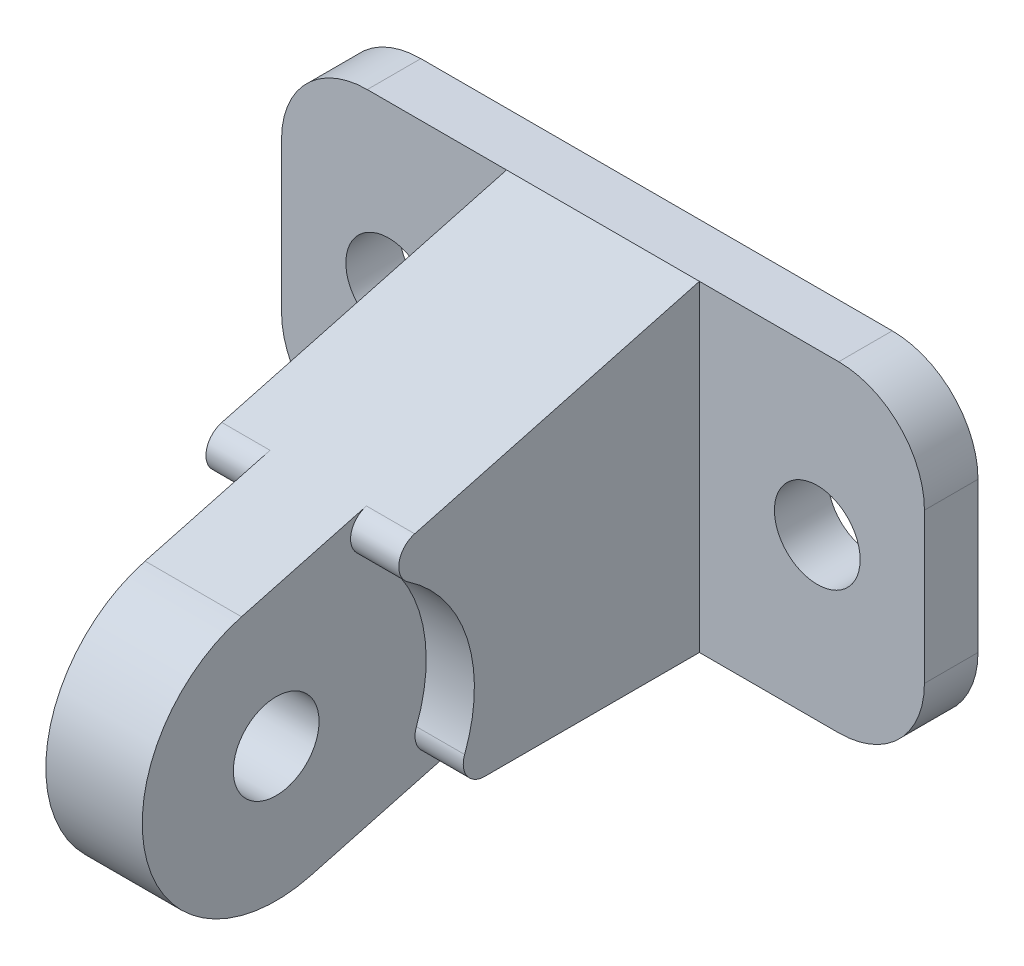
SolidWorks part; units mm, degrees
ref_plane "Front Plane" through (0, 0, 0) normal (0, 0, 1) x (1, 0, 0)
ref_plane "Top Plane" through (0, 0, 0) normal (0, 1, 0) x (1, 0, 0)
ref_plane "Right Plane" through (0, 0, 0) normal (1, 0, 0) x (0, 0, -1)
sketch "Sketch1" plane through (0, 0, 0) normal (0, 0, 1) x (1, 0, 0)
  line L1 (30, -15) -> (-30, -15)
  line L2 (30, -15) -> (30, 15)
  line L3 (30, 15) -> (-30, 15)
  line L4 (-30, -15) -> (-30, 15)
  line L5 (30, -15) -> (-30, 15) construction
  line L6 (30, 15) -> (-30, -15) construction
  point P0 (0, 0)
  dimension "D1" = 30
  dimension "D2" = 60
extrude "Boss-Extrude1" add sketch "Sketch1" along normal blind 5
sketch "Sketch3" plane through (0, 0, 0) normal (1, 0, 0) x (0, 0, -1)
  line L0 (-5, 15) -> (-31.5739, 7.8795)
  line L1 (-5, 15) -> (-5, -15)
  line L2 (-5, -15) -> (-25.0425, -15)
  line L3 (-5, 15) -> (0, 15) construction
  line L4 (-31.5739, 7.8795) -> (-43.2352, 4.7549)
  line L5 (-36.7648, -19.3932) -> (-20.3689, -15)
  arc A1 (-31.5739, 7.8795) -> (-32.1742, 4.2893) centre (-31.0563, 5.9477) ccw
  arc A2 (-25.0425, -15) -> (-26.9121, -12.2899) centre (-25.0425, -13) cw
  arc A3 (-26.9121, -12.2899) -> (-32.1742, 4.2893) centre (-40, -7.3192) ccw
  circle A4 centre (-40, -7.3192) radius 4
  circle A5 centre (-40, -7.3192) radius 12.5
  point P14 (-19.3881, -12.2899)
  point P16 (-40, -19.8192)
  point P18 (-21.4082, -15)
  point P19 (-45.0839, -21.5747)
  point P23 (-23.1859, -15)
  point P24 (-36.9289, -19.436)
  dimension "D2" = 2
  dimension "D3" = 14
  dimension "D5" = 8
  dimension "D6" = 25
  dimension "D1" = 15
  dimension "D4" = 40
extrude "Boss-Extrude2" add sketch "Sketch3" along normal mid plane 18 contours A3 A1 L0 L1 L2 A2
extrude "Boss-Extrude3" add sketch "Sketch3<3>" along normal mid plane 9 contours A5 A4 | A5 L5 L2 A2 A3 A1 L4 region at (0, 6.3362, 33.3799) region at (0, 2.3173, 32.6057)
sketch "Sketch3<3>" plane through (0, 0, 0) normal (1, 0, 0) x (0, 0, -1) same geometry as "Sketch3"
hole_wizard "Hole1" positions "Sketch4" profile "Sketch5" legacy end condition through all
sketch "Sketch4" plane through (0, 0, 5) normal (0, 0, 1) x (1, 0, 0)
  line L0 (0, 0) -> (0, 18.1868) construction
  point P0 (-20, 0)
  point P2 (20, 0)
  point P9 (0, 0)
  dimension "D1" = 40
sketch "Sketch5" plane through (-20, 0, 5) normal (1, 0, 0) x (0, -1, 0)
  line L0 (0, 0) -> (0, 5)
  line L1 (0, 5) -> (4, 5)
  line L2 (4, 5) -> (4, 0)
  line L3 (4, 0) -> (0, 0)
  line L4 (0, 110) -> (0, -10) construction
  dimension "Diameter" = 8
  dimension "Depth" = 5
fillet "Fillet1" radius 8 4 edges at (30, 15, 2.5) (30, -15, 2.5) (-30, 15, 2.5) (-30, -15, 2.5)
